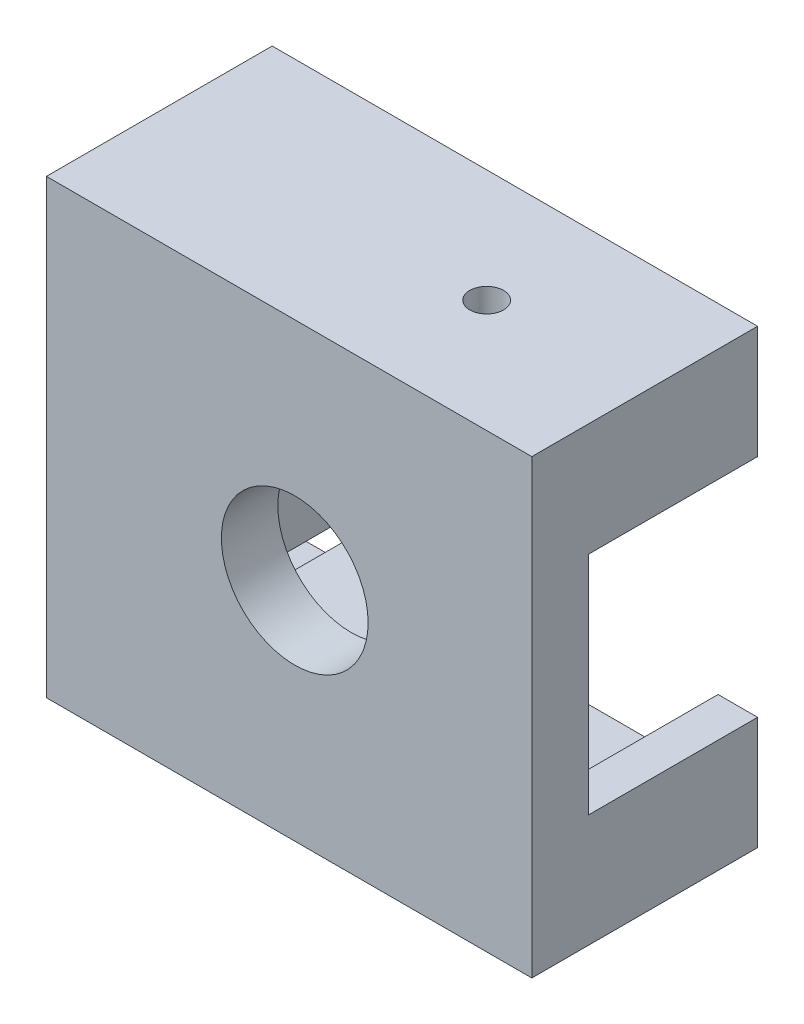
SolidWorks part; units mm, degrees
ref_plane "Front Plane" through (0, 0, 0) normal (0, 0, 1) x (1, 0, 0)
ref_plane "Top Plane" through (0, 0, 0) normal (0, 1, 0) x (1, 0, 0)
ref_plane "Right Plane" through (0, 0, 0) normal (1, 0, 0) x (0, 0, -1)
sketch "Sketch1" plane through (0, 0, 0) normal (0, 0, 1) x (1, 0, 0)
  line L0 (92.0048, 6.2146) -> (44.0048, 6.2146) construction
  line L1 (97.0048, 11.2146) -> (54.0048, 11.2146)
  line L2 (97.0048, 11.2146) -> (97.0048, -28.7854)
  line L3 (97.0048, -28.7854) -> (54.0048, -28.7854)
  line L4 (54.0048, 11.2146) -> (54.0048, -28.7854)
  line L5 (92.0048, 6.2146) -> (92.0048, -1.2854) construction
  dimension "D1" = 40
  dimension "D2" = 43
  dimension "D3" = 5
  dimension "D4" = 5
extrude "Boss-Extrude1" add sketch "Sketch1" along normal blind 5
sketch "Sketch2" plane through (0, 0, 0) normal (0, 0, -1) x (-1, 0, 0)
  line L0 (-97.0048, -28.7854) -> (-97.0048, 11.2146) construction
  line L5 (-72.5048, 0.5146) -> (-85.5048, 0.5146)
  line L6 (-72.5048, 0.5146) -> (-72.5048, -1.4854)
  line L7 (-72.5048, -1.4854) -> (-85.5048, -1.4854)
  line L8 (-85.5048, 0.5146) -> (-85.5048, -1.4854)
  line L13 (-68.0048, -15.9854) -> (-85.5048, -15.9854)
  line L15 (-68.0048, -17.9854) -> (-85.5048, -17.9854)
  line L16 (-85.5048, -15.9854) -> (-85.5048, -17.9854)
  line L17 (-54.0048, -28.7854) -> (-97.0048, -28.7854) construction
  line L18 (-97.0048, 11.2146) -> (-54.0048, 11.2146) construction
  line L19 (-68.0048, -15.9854) -> (-68.0048, -17.9854)
  line L25 (-68.0048, -4.2854) -> (-65.5048, -4.2854)
  line L26 (-68.0048, -4.2854) -> (-68.0048, -14.2854)
  line L27 (-68.0048, -14.2854) -> (-65.5048, -14.2854)
  line L28 (-65.5048, -4.2854) -> (-65.5048, -14.2854)
  point P18 (-66.7548, -14.2854)
  dimension "D1" = 2
  dimension "D2" = 13
  dimension "D3" = 11.5
  dimension "D4" = 10
  dimension "D5" = 2.5
  dimension "D6" = 2
  dimension "D7" = 17.5
  dimension "D8" = 14.5
  dimension "D9" = 10.8
  dimension "D10" = 11.5
  dimension "D11" = 29
  dimension "D12" = 10.7
extrude "Boss-Extrude3" add sketch "Sketch2" along normal blind 8 contours L26 L27 L28 L25 | L19 L15 L16 L13 | L6 L5 L8 L7
sketch "Sketch3" plane through (0, 0, 0) normal (0, 0, -1) x (-1, 0, 0)
  line L0 (-54.0048, 11.2146) -> (-97.0048, 11.2146)
  line L1 (-97.0048, 11.2146) -> (-97.0048, -28.7854)
  line L2 (-97.0048, -28.7854) -> (-54.0048, -28.7854)
  line L3 (-54.0048, -28.7854) -> (-54.0048, -25.2854)
  line L4 (-54.0048, 11.2146) -> (-54.0048, -28.7854) construction
  line L5 (-54.0048, -25.2854) -> (-93.5048, -25.2854)
  line L6 (-93.5048, -25.2854) -> (-93.5048, 7.7146)
  line L7 (-93.5048, 7.7146) -> (-54.0048, 7.7146)
  line L8 (-54.0048, 7.7146) -> (-54.0048, 11.2146)
  dimension "D1" = 3.5
  dimension "D2" = 3.5
  dimension "D3" = 3.5
extrude "Boss-Extrude4" add sketch "Sketch3" along normal blind 15
sketch "Sketch4" plane through (0, 11.2146, 0) normal (0, 1, 0) x (1, 0, 0)
  line L0 (97.0048, -5) -> (97.0048, 15) construction
  line L1 (97.0048, -5) -> (54.0048, -5) construction
  circle A0 centre (83.0048, 5) radius 1.5
  dimension "D1" = 14
  dimension "D2" = 10
  dimension "D3" = 3
extrude "Cut-Extrude1" cut sketch "Sketch4" against normal blind 65
sketch "Sketch6" plane through (0, -28.7854, 0) normal (0, -1, 0) x (1, 0, 0)
  line L0 (54.0048, 5) -> (54.0048, -15) construction
  circle A0 centre (60.0048, -5) radius 1.5
  circle A1 centre (83.0048, -5) radius 1.5 construction
  dimension "D1" = 0
  dimension "D2" = 6
  dimension "D3" = 3
extrude "Cut-Extrude2" cut sketch "Sketch6" against normal blind 10
sketch "Sketch7" plane through (0, 0, 5) normal (0, 0, 1) x (1, 0, 0)
  line L0 (54.0048, 11.2146) -> (54.0048, -28.7854) construction
  line L1 (97.0048, 11.2146) -> (54.0048, 11.2146) construction
  circle A0 centre (76.0048, -8.7854) radius 6.5
  dimension "D1" = 13
  dimension "D2" = 22
  dimension "D3" = 20
extrude "Cut-Extrude3" cut sketch "Sketch7" against normal blind 20
sketch "Sketch8" plane through (97.0048, 0, 0) normal (1, 0, 0) x (0, 0, -1)
  line L0 (15, 11.2146) -> (15, -28.7854) construction
  line L1 (15, 1.2146) -> (0, 1.2146)
  line L2 (15, 1.2146) -> (15, -18.7854)
  line L3 (15, -18.7854) -> (0, -18.7854)
  line L4 (0, 1.2146) -> (0, -18.7854)
  line L5 (-5, -28.7854) -> (-5, 11.2146) construction
  point P8 (-5, -8.7854)
  dimension "D1" = 20
  dimension "D2" = 10
  dimension "D3" = 15
extrude "Cut-Extrude4" cut sketch "Sketch8" against normal blind 5
